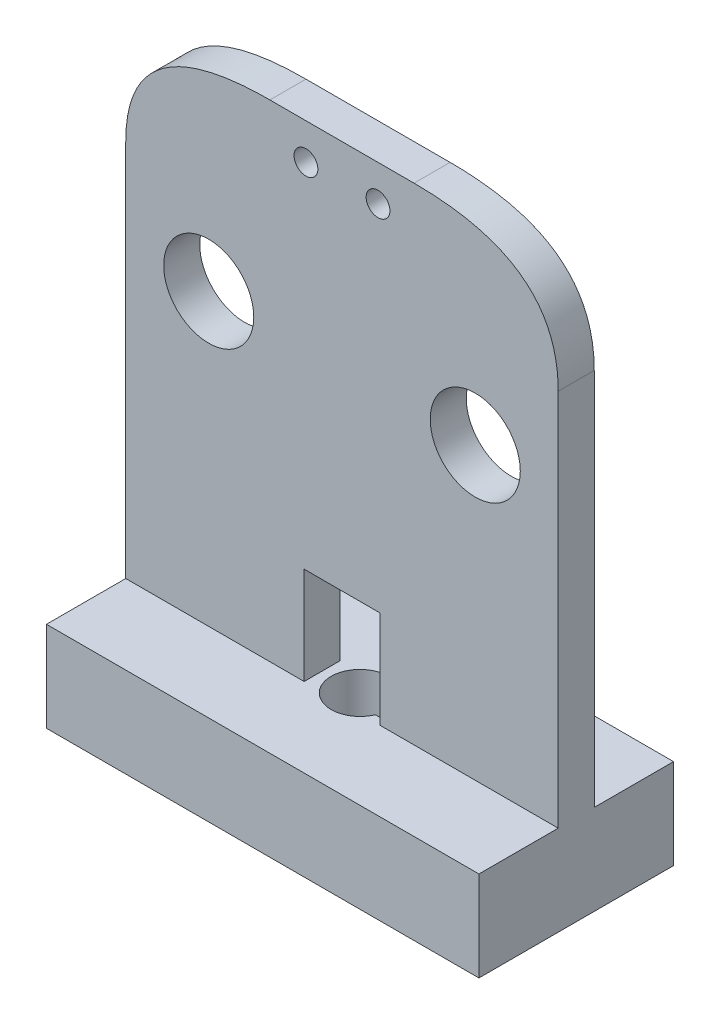
SolidWorks part; units mm, degrees
ref_plane "Ebene vorne" through (0, 0, 0) normal (0, 0, 1) x (1, 0, 0)
ref_plane "Ebene oben" through (0, 0, 0) normal (0, 1, 0) x (1, 0, 0)
ref_plane "Ebene rechts" through (0, 0, 0) normal (1, 0, 0) x (0, 0, -1)
sketch "Skizze1" plane through (0, 0, 0) normal (0, 0, 1) x (1, 0, 0)
  line L0 (-5, 35) -> (5, 35)
  line L1 (-30, -40) -> (30, -40)
  line L2 (-30, -40) -> (-30, 40)
  line L3 (-30, 40) -> (30, 40)
  line L4 (30, -40) -> (30, 40)
  line L5 (-30, -40) -> (30, 40) construction
  line L6 (-30, 40) -> (30, -40) construction
  line L7 (18.4881, 12.7723) -> (-18.4881, 12.7723)
  line L8 (-5, 35) -> (-18.4881, 12.7723)
  circle A0 centre (-5, 35) radius 1.65
  circle A1 centre (5, 35) radius 1.65
  circle A2 centre (-18.4881, 12.7723) radius 6.25
  circle A3 centre (18.4881, 12.7723) radius 6.25
  point P0 (0, 0)
  point P13 (0, 0)
  point P14 (0, 35)
  point P17 (0, 12.7723)
  dimension "D3" = 3.3
  dimension "D4" = 3.3
  dimension "D7" = 12.5
  dimension "D8" = 12.5
  dimension "D1" = 60
  dimension "D2" = 80
  dimension "D5" = 5
  dimension "D6" = 5
  dimension "D9" = 58.75
  dimension "D10" = 26
extrude "Aufsatz-Linear austragen1" add sketch "Skizze1" along normal blind 5 contours L1 L4 L3 L2 A3 A2 A1 A0 region at (0, -0.8228, 0)
sketch "Skizze2" plane through (0, 0, 5) normal (0, 0, 1) x (1, 0, 0)
  line L0 (30, -40) -> (30, 40) construction
  line L1 (-30, -40) -> (30, -40)
  line L2 (-30, -40) -> (-30, -27.5)
  line L3 (-30, -27.5) -> (30, -27.5)
  line L4 (30, -40) -> (30, -27.5)
  line L5 (-30, -40) -> (30, -27.5) construction
  line L6 (-30, -27.5) -> (30, -40) construction
  line L7 (-30, -40) -> (-30, 40) construction
  line L8 (-30, -40) -> (30, -40) construction
  point P4 (0, -33.75)
  dimension "D1" = 12.5
fillet "Verrundung1" radius 20 2 edges at (30, 40, 2.5) (-30, 40, 2.5) second distance 15 conic rho 0.5 first distance on face at (0, 40, 2.5)
extrude "Aufsatz-Linear austragen2" add sketch "Skizze2" along normal blind 11 and the other way blind 16
sketch "Skizze3" plane through (0, -40, 0) normal (0, -1, 0) x (1, 0, 0)
  line L0 (-30, 2.5) -> (30, 2.5) construction
  line L1 (-4, 2.5) -> (-4, 5.542) construction
  line L2 (2.8, 0.95) -> (5.2, 0.95)
  line L3 (2.8, 0.95) -> (2.8, 4.05)
  line L4 (2.8, 4.05) -> (5.2, 4.05)
  line L5 (5.2, 0.95) -> (5.2, 4.05)
  line L6 (2.8, 0.95) -> (5.2, 4.05) construction
  line L7 (2.8, 4.05) -> (5.2, 0.95) construction
  line L8 (-30, 16) -> (-30, -11) construction
  line L9 (30, 16) -> (30, -11) construction
  line L10 (-30, 2.5) -> (-29.124, 2.5) construction
  circle A0 centre (0, 2.5) radius 4
  point P4 (4, 2.5)
  dimension "D1" = 8
  dimension "D2" = 3.1
  dimension "D3" = 9.2
extrude "Schnitt-Linear austragen1" cut sketch "Skizze3" against normal blind 13 contours L4 A0 L2 L3 | A0 L2 L5 L4 | L2 A0 L4 L3 region at (3.3527, -40, 2.5) region at (-0.2434, -40, 2.5) region at (4.5455, -40, 2.5)
sketch "Skizze4" plane through (0, -27, 0) normal (0, -1, 0) x (1, 0, 0)
  line L1 (-5.25, -2.75) -> (5.25, -2.75)
  line L2 (-5.25, -2.75) -> (-5.25, 7.75)
  line L3 (-5.25, 7.75) -> (5.25, 7.75)
  line L4 (5.25, -2.75) -> (5.25, 7.75)
  line L5 (-5.25, -2.75) -> (5.25, 7.75) construction
  line L6 (-5.25, 7.75) -> (5.25, -2.75) construction
  arc A1 (3.6875, 4.05) -> (3.6875, 0.95) centre (0, 2.5) ccw construction
  point P0 (0, 2.5)
  point P1 (0, 2.5)
  point P6 (0, 0)
  dimension "D1" = 10.5
  dimension "D2" = 10.5
extrude "Schnitt-Linear austragen2" cut sketch "Skizze4" against normal blind 13 and the other way up to surface (0.5 mm away) other way up to face at (0, -27.5, 8.9167)
